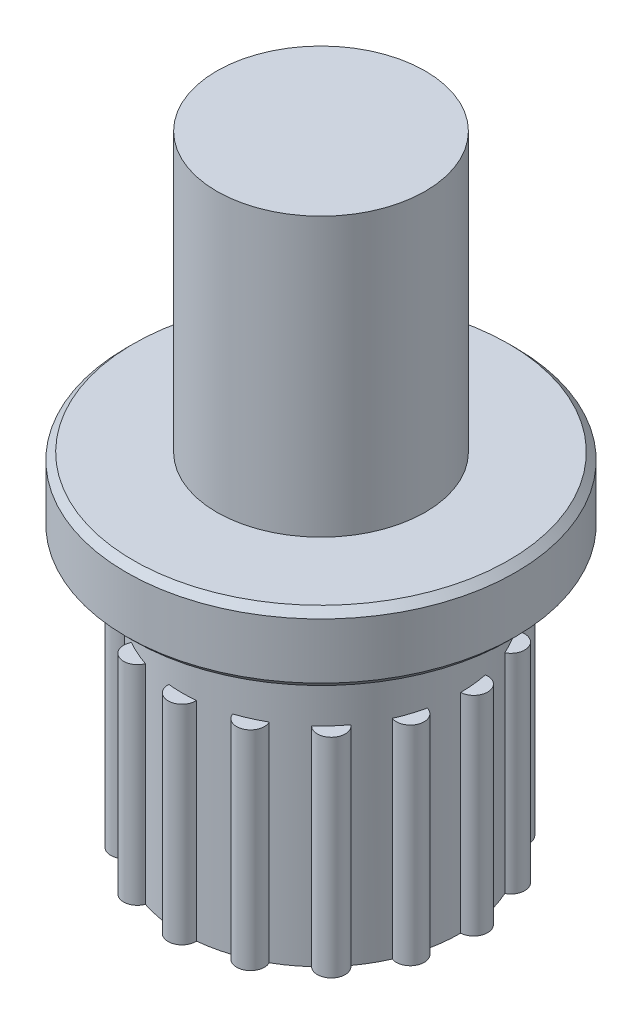
SolidWorks part; units mm, degrees
ref_plane "Front Plane" through (0, 0, 0) normal (0, 0, 1) x (1, 0, 0)
ref_plane "Top Plane" through (0, 0, 0) normal (0, 1, 0) x (1, 0, 0)
ref_plane "Right Plane" through (0, 0, 0) normal (1, 0, 0) x (0, 0, -1)
sketch "Sketch2" plane through (0, 0, 0) normal (1, 0, 0) x (0, 0, -1)
  line L0 (0, 0) -> (10, 0)
  line L1 (10, 0) -> (10, 20)
  line L2 (10, 20) -> (14, 20)
  line L3 (14, 20) -> (14, 25)
  line L4 (14, 25) -> (7.5, 25)
  line L5 (7.5, 25) -> (7.5, 45)
  line L6 (7.5, 45) -> (0, 45)
  line L7 (0, 45) -> (0, 0)
  dimension "D1" = 7.5
  dimension "D2" = 14
  dimension "D3" = 10
  dimension "D4" = 20
  dimension "D5" = 5
  dimension "D6" = 20
revolve "Revolve1" add sketch "Sketch2" angle 360 about L7
ref_axis "Axis1" through (0, 25, 0) along (0, 1, 0)
sketch "Sketch3" plane through (0, 0, 0) normal (0, -1, 0) x (1, 0, 0)
  circle A0 centre (0, 10) radius 1
  circle A1 centre (0, 0) radius 10 construction
  circle A2 centre (0, 0) radius 10 construction
  dimension "D1" = 2
extrude "Boss-Extrude1" add sketch "Sketch3" against normal offset from surface (15 mm away) 5 up to face at (0, 20, 14)
pattern_circular "CirPattern1" count 15 over 360 about axis through (0, 25, 0) along (0, 1, 0) of "Boss-Extrude1"
chamfer "Chamfer1" distance 0.5 angle 45 2 edges at (0, 25, 14) (0, 20, 14)
